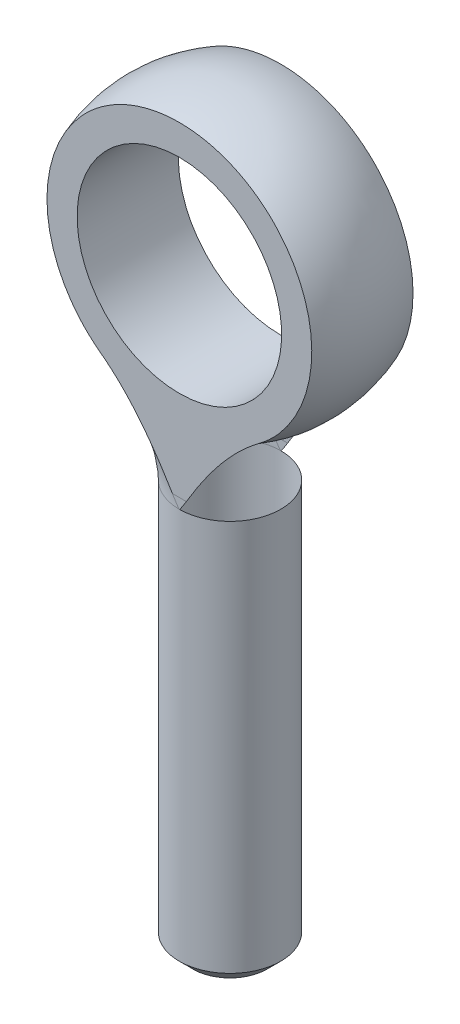
SolidWorks part; units mm, degrees
material "Plain Carbon Steel"
ref_plane "Front" through (0, 0, 0) normal (0, 0, 1) x (1, 0, 0)
ref_plane "Top" through (0, 0, 0) normal (0, 1, 0) x (1, 0, 0)
ref_plane "Right" through (0, 0, 0) normal (1, 0, 0) x (0, 0, -1)
sketch "Sketch1" plane through (0, 0, 0) normal (0, 0, 1) x (1, 0, 0)
  line L0 (0, 0) -> (0, -31.75)
  line L1 (0, -31.75) -> (3.9751, -31.75)
  line L2 (3.9751, -31.75) -> (3.9751, 0)
  line L3 (3.9751, 0) -> (0, 0)
  line L5 (0, 26.9875) -> (0, 0) construction
  line L6 (0, 26.9875) -> (11.1125, 26.9875) construction
  line L7 (11.1125, 26.9875) -> (11.1125, 15.875) construction
  line L8 (-3.9751, -31.75) -> (-3.9751, 0) construction
  line L9 (4.0898, -31.6838) -> (4.0898, -32.743)
  line L10 (4.0898, -32.743) -> (3.1725, -32.2134)
  line L11 (3.2871, -32.2796) -> (3.2871, -32.1472)
  line L12 (3.1725, -32.2134) -> (4.0898, -31.6838)
  line L13 (4.0324, -31.7169) -> (4.0324, -32.7099)
  line L14 (4.0898, -32.2134) -> (3.9751, -32.2134)
  line L15 (3.9751, -31.75) -> (3.9751, -32.6768)
  line L16 (3.1725, -32.2134) -> (3.2871, -32.2134)
  arc A0 (7.3754, 7.5629) -> (0, 26.9875) centre (0, 15.875) ccw construction
  circle A1 centre (0, 15.875) radius 3.9688 construction
  circle A2 centre (0, 15.875) radius 7.9375 construction
  circle A3 centre (0, 15.875) radius 8.0169 construction
  arc A4 (3.9751, 0) -> (7.3754, 7.5629) centre (14.0859, 0) cw construction
  point P24 (0, 23.8125)
  point P26 (3.9751, -32.2134)
  point P28 (4.0324, -32.2134)
  dimension "A" = 7.9375
  dimension "Ball Dia" = 15.875
  dimension "B" = 22.225
  dimension "D1" = 16.0337
  dimension "D" = 47.625
  dimension "E" = 31.75
  dimension "Thread Dia" = 7.9502
  dimension "D2" = 60
  dimension "Pitch" = 1.0592
  dimension "D4" = 0.1324
sketch "Sketch2" plane through (0, 0, 0) normal (1, 0, 0) x (0, 0, -1)
  line L0 (3.9688, 15.875) -> (-3.9687, 15.875)
  line L1 (3.9688, 16.6464) -> (0, 15.875) construction
  line L2 (3.9688, 15.1036) -> (0, 15.875) construction
  line L6 (5.5563, 15.875) -> (-5.5562, 15.875)
  line L7 (0, 11.9063) -> (0, 19.8438)
  line L8 (0, 26.9875) -> (0, 0) construction
  line L9 (0, 19.8438) -> (0, 11.9063) construction
  circle A0 centre (0, 15.875) radius 7.9375
  circle A1 centre (0, 15.875) radius 11.1125
  point P4 (0, 15.875)
  point P7 (0, 23.8125)
  point P9 (0, 7.9375)
  point P14 (0, 15.875)
  point P18 (0, 15.875)
  point P23 (11.1125, 15.875)
  point P25 (-11.1125, 15.875)
  dimension "OAWidth" = 7.9375
  dimension "Swivel" = 22
  dimension "BallWidth" = 11.1125
sketch "Sketch15" plane through (0, 0, 0) normal (0, 0, 1) x (1, 0, 0)
  line L0 (0, 26.9875) -> (0, 0) construction
  line L1 (11.1125, 26.9875) -> (-11.1125, 26.9875)
  line L2 (11.1125, 26.9875) -> (11.1125, 0)
  line L3 (11.1125, 0) -> (-11.1125, 0)
  line L4 (-11.1125, 26.9875) -> (-11.1125, 0)
  line L5 (3.9751, 0) -> (0, 0) construction
  point P5 (0, 26.9875)
sketch "Sketch14" plane through (0, 0, 0) normal (0, 0, 1) x (1, 0, 0)
  line L1 (0, 0) -> (0, -31.75) construction
  line L2 (0, -31.75) -> (3.9751, -31.75) construction
  line L3 (3.9751, -31.75) -> (3.9751, 0) construction
  line L5 (0, 0) -> (0, -31.75)
  line L6 (0, -31.75) -> (3.9751, -31.75)
  line L7 (3.9751, -31.75) -> (3.9751, 0)
  line L8 (3.9751, 0) -> (0, 0) construction
  line L9 (3.9751, 0) -> (0, 0)
revolve "Revolve4" add sketch "Sketch14" angle 360 about L0
sketch "Sketch21" plane through (0, 0, 0) normal (0, 0, 1) x (1, 0, 0)
  line L0 (0, 26.9875) -> (0, 0) construction
  line L1 (3.9751, 0) -> (0, 0) construction
  line L2 (0, 26.9875) -> (0, 0)
  line L3 (3.9751, 0) -> (0, 0)
  arc A0 (7.3754, 7.5629) -> (3.9751, 0) centre (14.0859, 0) ccw construction
  arc A1 (7.3754, 7.5629) -> (0, 26.9875) centre (0, 15.875) ccw construction
  arc A2 (7.3754, 7.5629) -> (3.9751, 0) centre (14.0859, 0) ccw
  arc A3 (7.3754, 7.5629) -> (0, 26.9875) centre (0, 15.875) ccw
revolve "Revolve5" add sketch "Sketch21" angle 360 about L0
sketch "Sketch24" plane through (0, 0, 0) normal (1, 0, 0) x (0, 0, -1)
  line L0 (3.9688, 15.875) -> (3.9688, 26.9875)
  line L1 (3.9688, 26.9875) -> (11.1125, 26.9875)
  line L2 (11.1125, 0) -> (11.1125, 26.9875)
  line L3 (3.9688, 15.875) -> (3.9688, 0.7937)
  line L4 (3.9688, 0.7937) -> (3.9751, 0)
  line L5 (3.9751, 0) -> (11.1125, 0)
  line L6 (0, 26.9875) -> (0, 0) construction
  line L7 (0, 26.9875) -> (0, 0) construction
  line L8 (-3.9751, 0) -> (-11.1125, 0)
  line L9 (-3.9687, 0.7937) -> (-3.9751, 0)
  line L10 (-3.9687, 15.875) -> (-3.9687, 0.7937)
  line L11 (-11.1125, 0) -> (-11.1125, 26.9875)
  line L12 (-3.9688, 26.9875) -> (-11.1125, 26.9875)
  line L13 (-3.9687, 15.875) -> (-3.9688, 26.9875)
  dimension "D1" = 0.7937
extrude "Cut-Extrude10" cut sketch "Sketch24" against normal through all both and the other way through all
sketch "Sketch17" plane through (0, 0, 0) normal (0, 0, 1) x (1, 0, 0)
  circle A2 centre (0, 15.875) radius 8.0169 construction
  circle A3 centre (0, 15.875) radius 8.0169
extrude "Cut-Extrude9" cut sketch "Sketch17" against normal through all both and the other way through all
sketch "Sketch7" plane through (0, 0, 0) normal (0, 0, 1) x (1, 0, 0)
  line L0 (0, 23.8125) -> (0, 7.9375)
  line L1 (0, 26.9875) -> (0, 0) construction
  line L2 (0, 0) -> (0, 7.9375) construction
  arc A0 (0, 7.9375) -> (0, 23.8125) centre (0, 15.875) ccw
  circle A1 centre (0, 15.875) radius 7.9375 construction
revolve "Revolve3" add sketch "Sketch7" angle 360 about L2
sketch "Sketch10" plane through (0, 0, 0) normal (0, 0, 1) x (1, 0, 0)
  circle A0 centre (0, 15.875) radius 3.9688 construction
  circle A1 centre (0, 15.875) radius 3.9688
extrude "Cut-Extrude4" cut sketch "Sketch10" against normal through all and the other way through all
sketch "Sketch22" plane through (0, 0, 0) normal (0, 0, 1) x (1, 0, 0)
  line L0 (-11.1125, 26.9875) -> (-11.1125, 0) construction
  line L1 (11.1125, 0) -> (-11.1125, 0) construction
  line L2 (11.1125, 26.9875) -> (11.1125, 0) construction
  line L3 (11.1125, 26.9875) -> (-11.1125, 26.9875) construction
  line L4 (-11.1125, 26.9875) -> (-11.1125, 0)
  line L5 (11.1125, 0) -> (-11.1125, 0)
  line L6 (11.1125, 26.9875) -> (11.1125, 0)
  line L7 (11.1125, 26.9875) -> (-11.1125, 26.9875)
extrude "Cut-Extrude7" cut sketch "Sketch22" against normal through all from vertex starting at point (0, 15.875, -5.5563)
sketch "Sketch23" plane through (0, 0, 0) normal (0, 0, 1) x (1, 0, 0)
  line L0 (-11.1125, 26.9875) -> (-11.1125, 0) construction
  line L1 (11.1125, 0) -> (-11.1125, 0) construction
  line L2 (11.1125, 26.9875) -> (11.1125, 0) construction
  line L3 (11.1125, 26.9875) -> (-11.1125, 26.9875) construction
  line L4 (-11.1125, 26.9875) -> (-11.1125, 0)
  line L5 (11.1125, 0) -> (-11.1125, 0)
  line L6 (11.1125, 26.9875) -> (11.1125, 0)
  line L7 (11.1125, 26.9875) -> (-11.1125, 26.9875)
extrude "Cut-Extrude8" cut sketch "Sketch23" along normal through all from vertex starting at point (0, 15.875, 5.5562)
chamfer "Chamfer1" distance 1.0592 angle 45 1 edges at (-3.9751, -31.75, 0)
chamfer "Chamfer2" distance 0.3969 angle 45 2 edges at (3.9688, 15.875, 5.5562) (3.9688, 15.875, -5.5563)
sketch "Sketch18" [suppressed] plane through (0, -31.75, 0) normal (0, -1, 0) x (1, 0, 0)
  circle A0 centre (0, 0) radius 3.9751 construction
  circle A1 centre (0, 0) radius 3.9751
curve "Helix/Spiral1" [suppressed] pitch 1.0592 height 32.8092 turns 30.976
sketch "Sketch19" [suppressed] plane through (0, 0, 0) normal (0, 0, 1) x (1, 0, 0)
  line L0 (3.2871, -32.2796) -> (3.2871, -32.1472) construction
  line L1 (3.1725, -32.2134) -> (4.0898, -31.6838) construction
  line L2 (4.0898, -32.743) -> (3.1725, -32.2134) construction
  line L3 (4.0324, -31.7169) -> (4.0324, -32.7099) construction
  line L4 (3.2871, -32.2796) -> (3.2871, -32.1472)
  line L5 (3.2871, -32.1472) -> (4.0324, -31.7169)
  line L6 (4.0324, -32.7099) -> (3.2871, -32.2796)
  line L7 (4.0324, -31.7169) -> (4.0324, -32.7099)
sweep "Cut-Sweep1" [suppressed] cut profiles "Sketch19" path "Helix/Spiral1"
ref_plane "Plane1" [suppressed] through (0, 0, 0) normal (0, 1, 0) x (1, 0, 0)
sketch "Sketch20" [suppressed] plane through (0, 0, 0) normal (0, 1, 0) x (1, 0, 0)
  circle A0 centre (0, 0) radius 3.9751
extrude "Boss-Extrude2" [suppressed] add sketch "Sketch20" against normal through all draft 60
combine bodies "Combine1" [suppressed] operation type add bodies to combine 130 133
delete or keep bodies "Body-Delete/Keep 1" type delete bodies bodies 132
combine bodies "Combine2" operation type add bodies to combine 133 122
ref_plane "Plane2" through (0, 0, -3.9688) normal (0, 0, -1) x (-1, 0, 0)
equation "\"D1@Sketch1\"=\"Ball Dia@Sketch1\"*1.01"
equation "\"D1\"= \"A@Sketch1\" / 20"
equation "\"D3\"= \"E@Sketch1\" + .2"
equation "\"D4@Sketch1\"=\"Pitch@Sketch1\"/8"
equation "\"D1@Chamfer1\"=\"Pitch@Sketch1\""
equation "\"D4@Helix/Spiral1\"=\"Pitch@Sketch1\""
equation "\"D3@Helix/Spiral1\"=\"E@Sketch1\"+\"Pitch@Sketch1\""
equation "\"D1@Chamfer2\"=\"A@Sketch1\"/20"
equation "\"D1@Sketch24\"=(\"OAWidth@Sketch2\"/2)/5"
